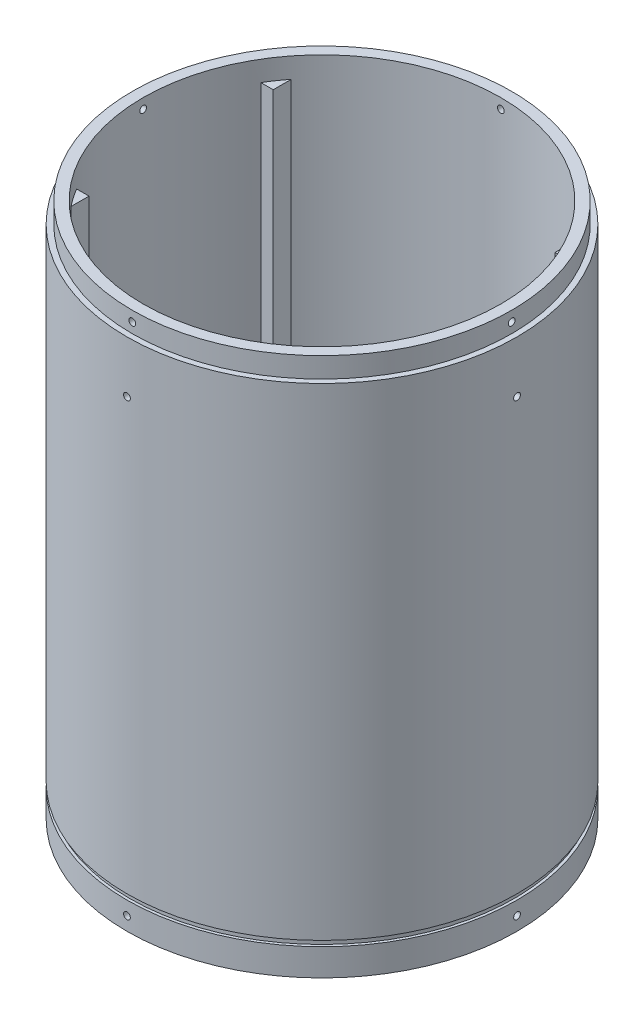
SolidWorks part; units mm, degrees
ref_plane "前基準面" through (0, 0, 0) normal (0, 0, 1) x (1, 0, 0)
ref_plane "上基準面" through (0, 0, 0) normal (0, 1, 0) x (1, 0, 0)
ref_plane "右基準面" through (0, 0, 0) normal (1, 0, 0) x (0, 0, -1)
sketch "草圖6" plane through (0, 0, 0) normal (0, 1, 0) x (1, 0, 0)
  line L0 (0, 0) -> (-95.9878, 0) construction
  line L1 (0, 0) -> (-70, 0) construction
  circle A0 centre (0, 0) radius 66
  circle A1 centre (0, 0) radius 70
  circle A2 centre (0, 0) radius 72
  point P5 (-70, 0)
  point P10 (0, 70)
  point P11 (70, 0)
  point P12 (0, -70)
  dimension "D1" = 2
  dimension "D2" = 4
  dimension "D3" = 144
  dimension "D4" = 4
  dimension "D5" = 70
sketch "草圖7" plane through (0, 0, 0) normal (0, 1, 0) x (1, 0, 0)
  line L1 (-34, 34) -> (34, 34)
  line L2 (-34, 34) -> (-34, -34)
  line L3 (-34, -34) -> (34, -34)
  line L4 (34, 34) -> (34, -34)
  line L5 (-34, 34) -> (34, -34) construction
  line L6 (-34, -34) -> (34, 34) construction
  point P0 (0, 0)
  point P7 (-30, 30)
  point P10 (30, 30)
  point P11 (30, -30)
  point P12 (-30, -30)
  point P13 (0, 0)
  dimension "D1" = 68
  dimension "D2" = 4
  dimension "D3" = 4
extrude "填料-伸長1" add sketch "草圖6" along normal blind 190 contours A2 A1 region at (-71.7964, 0, 0)
extrude "填料-伸長2" add sketch "草圖6<15>" along normal blind 197.5 contours A1 A0 region at (-68.0201, 0, 0)
sketch "草圖6<15>" plane through (0, 0, 0) normal (0, 1, 0) x (1, 0, 0) same geometry as "草圖6"
extrude "填料-伸長3" add sketch "草圖6<16>" along normal blind 3 contours A0 region at (0, 0, 0)
sketch "草圖6<16>" plane through (0, 0, 0) normal (0, 1, 0) x (1, 0, 0) same geometry as "草圖6"
sketch "草圖9" plane through (0, 0, 0) normal (0, 1, 0) x (1, 0, 0)
  line L0 (0, 0) -> (0, 39.247) construction
  line L1 (52, 67.0867) -> (52, -71.5265)
  line L2 (-96.5637, -34) -> (97.4044, -34)
  line L4 (-52, 67.0867) -> (-52, -71.5265)
  line L5 (-56.5685, 34) -> (88.304, 34)
  circle A0 centre (0, 0) radius 66
  circle A1 centre (0, 0) radius 70
  circle A2 centre (0, 0) radius 72
  dimension "D1" = 2
  dimension "D2" = 4
  dimension "D3" = 144
  dimension "D4" = 52
extrude "填料-伸長6" add sketch "草圖9" along normal up to surface (190 mm away) contours L4 A0 L5 | L2 A0 L4 | L1 A0 L2 | L5 A0 L1 region at (53.5564, 0, -36.2624) region at (-53.5564, 0, -36.2624) region at (53.5564, 0, 36.2624) region at (-53.5564, 0, 36.2624) up to face at (0, 190, 70)
sketch "草圖30" plane through (0, 0, 0) normal (1, 0, 0) x (0, 0, -1)
  line L0 (0, 197.5) -> (0, 190) construction
  line L1 (70, 197.5) -> (-70, 197.5) construction
  line L2 (72, 190) -> (-72, 190) construction
  point P6 (0, 193.75)
  dimension "D1" = 3.75
hole_wizard "Ø2.5mm 定位孔3" positions "3D草圖17" profile "草圖31" hole size "Ø2.5" standard "JIS" end condition up to next
sketch3d "3D草圖17"
  point P0 (70, 193.75, 0)
sketch "草圖31" plane through (70, 193.75, 0) normal (0, 1, 0) x (0, 0, -1)
  line L0 (0, 0) -> (0, 70)
  line L1 (0, 70) -> (1.25, 70)
  line L2 (1.25, 70) -> (1.25, 0)
  line L5 (1.25, 0) -> (0, 0)
  line L11 (0, -6.35) -> (0, 107.95) construction
  dimension "貫穿孔直徑" = 2.5
  dimension "貫穿孔深度" = 70
pattern_circular "環狀複製排列1" count 4 over 360 about axis through (0, 197.5, 0) along (0, 1, 0) of "Ø2.5mm 定位孔3"
ref_plane "平面4" through (0, 0, 0) normal (0, 0, 1) x (1, 0, 0)
sketch "草圖33" plane through (0, 0, 0) normal (0, 0, 1) x (1, 0, 0)
  line L5 (-72, 12) -> (-71, 12)
  line L6 (-71, 12) -> (-71, 10)
  line L7 (-71, 10) -> (-72, 10)
  line L9 (72, 0) -> (-72, 0) construction
  line L10 (-72, 12) -> (-72, 10)
  line L11 (-72, 190) -> (-72, 0) construction
  dimension "D1" = 1
  dimension "D2" = 2
  dimension "D6" = 10
revolve "除料-旋轉1" cut sketch "草圖33" angle 360 about L0
sketch "草圖35" plane through (0, 0, 0) normal (0, 0, 1) x (1, 0, 0)
  line L0 (-72, 10) -> (-72, 0) construction
  point P0 (-72, 5)
hole_wizard "Ø2.5mm 定位孔4" positions "3D草圖20" profile "草圖37" hole size "Ø2.5" standard "JIS"
sketch3d "3D草圖20"
  point P0 (-72, 5, 0)
sketch "草圖37" plane through (-72, 5, 0) normal (0, 1, 0) x (0, 0, 1)
  line L0 (0, 0) -> (0, 4.7511)
  line L1 (0, 4.7511) -> (1.25, 4)
  line L2 (1.25, 4) -> (1.25, 0)
  line L5 (1.25, 0) -> (0, 0)
  line L10 (0, 4.7511) -> (-1.25, 4) construction
  line L11 (0, -6.35) -> (0, 107.95) construction
  dimension "鑽孔直徑" = 2.5
  dimension "鑽孔深度" = 4
  dimension "導頭角度" = 118
pattern_circular "環狀複製排列2" count 4 over 360 about axis through (0, 197.5, 0) along (0, -1, 0) of "Ø2.5mm 定位孔4"
hole_wizard "Ø2.5mm 定位孔5" positions "3D草圖21" profile "草圖38" hole size "Ø2.5" standard "JIS"
sketch3d "3D草圖21"
  point P0 (-72, 170.9018, 0)
sketch "草圖38" plane through (-72, 170.9018, 0) normal (0, 1, 0) x (0, 0, 1)
  line L0 (0, 0) -> (0, 4.7511)
  line L1 (0, 4.7511) -> (1.25, 4)
  line L2 (1.25, 4) -> (1.25, 0)
  line L5 (1.25, 0) -> (0, 0)
  line L10 (0, 4.7511) -> (-1.25, 4) construction
  line L11 (0, -6.35) -> (0, 107.95) construction
  dimension "鑽孔直徑" = 2.5
  dimension "鑽孔深度" = 4
  dimension "導頭角度" = 118
pattern_circular "環狀複製排列3" count 4 over 360 about axis through (0, 197.5, 0) along (0, -1, 0) of "Ø2.5mm 定位孔5"
sketch "草圖39" plane through (0, 0, 0) normal (0, 1, 0) x (1, 0, 0)
  line L0 (-56.5685, 34) -> (56.5685, 34)
  line L2 (-56.5685, -34) -> (56.5685, -34)
  line L5 (0, 0) -> (0, 19.0172) construction
  line L6 (0, 0) -> (-12.2861, 0) construction
  line L7 (-56.707, 13) -> (-56.707, -13)
  line L8 (-64.707, 13) -> (64.707, 13)
  line L9 (56.707, 13) -> (56.707, -13)
  line L10 (-64.707, -13) -> (64.7924, -12.5675)
  arc A0 (-64.707, -13) -> (-56.5685, -34) centre (0, 0) ccw
  arc A3 (-56.5685, 34) -> (-64.707, 13) centre (0, 0) ccw
  arc A4 (64.707, 13) -> (56.5685, 34) centre (0, 0) ccw
  arc A5 (56.5685, -34) -> (64.7924, -12.5675) centre (0, 0) ccw
  point P12 (-49, 22)
  point P24 (56.707, 0)
  point P27 (-56.707, 0)
  dimension "D1" = 8
  dimension "D2" = 13
  dimension "D5" = 12
sketch "草圖40" plane through (0, 3, 0) normal (0, 1, 0) x (1, 0, 0)
  line L0 (-34, 34) -> (34, 34) construction
  line L1 (-36, 55.3173) -> (36, 55.3173)
  line L2 (-36, 55.3173) -> (-36, 34)
  line L3 (-36, 34) -> (36, 34)
  line L4 (36, 55.3173) -> (36, 34)
  line L5 (-36, 55.3173) -> (36, 34) construction
  line L6 (-36, 34) -> (36, 55.3173) construction
  circle A1 centre (0, 0) radius 66 construction
  point P0 (0, 44.6586)
  dimension "D1" = 21.3173
  dimension "D2" = 72
sketch "草圖41" plane through (0, 3, 0) normal (0, 1, 0) x (1, 0, 0)
  line L0 (0, 0) -> (-95.9878, 0) construction
  line L1 (-63.7154, 5.5) -> (56.2846, 5.5)
  line L2 (-63.7154, 5.5) -> (-63.7154, -5.5)
  line L3 (-63.7154, -5.5) -> (56.2846, -5.5)
  line L4 (56.2846, 5.5) -> (56.2846, -5.5)
  line L5 (-63.7154, 5.5) -> (56.2846, -5.5) construction
  line L6 (-63.7154, -5.5) -> (56.2846, 5.5) construction
  point P0 (-3.7154, 0)
  dimension "D1" = 11
  dimension "D2" = 120
extrude "填料-伸長8" add sketch "草圖40" along normal blind 70 separate body
